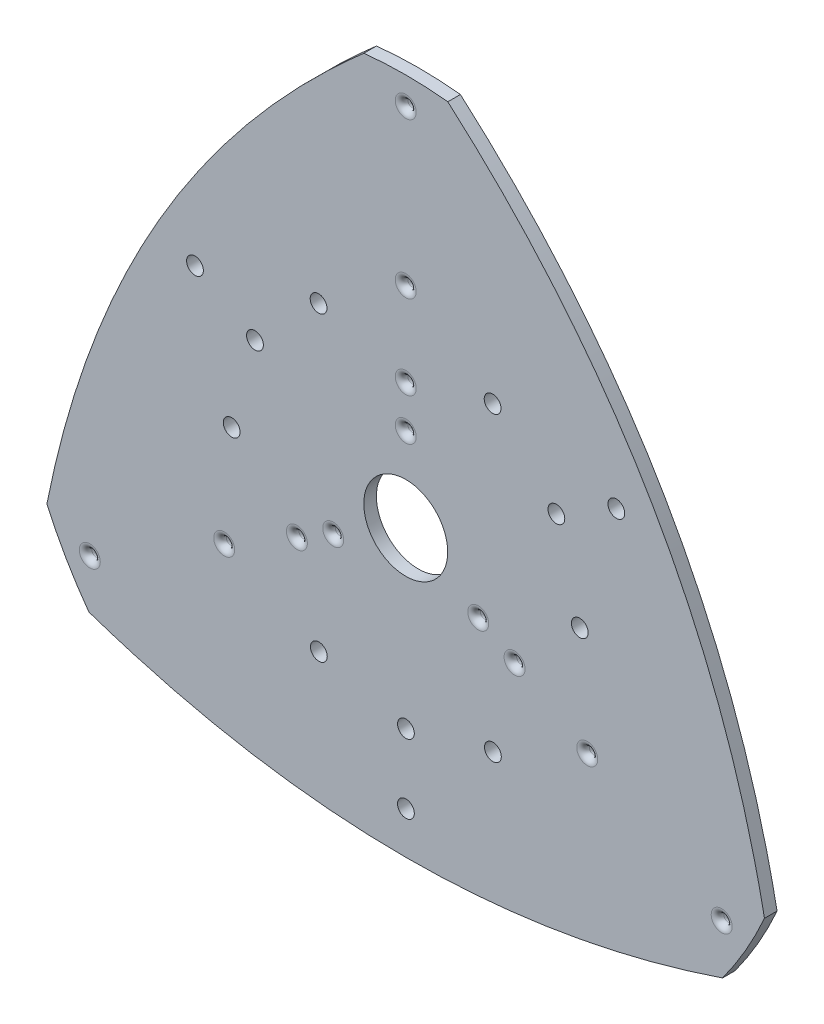
SolidWorks part; units mm, degrees
note: '?' marks a value the reader was unsure of.
ref_plane "前视基准面" through (0, 0, 0) normal (0, 0, 1) x (1, 0, 0)
ref_plane "上视基准面" through (0, 0, 0) normal (0, 1, 0) x (1, 0, 0)
ref_plane "右视基准面" through (0, 0, 0) normal (1, 0, 0) x (0, 0, -1)
other "Configuration Table"
sketch "草图1" plane through (0, 0, 0) normal (0, 0, 1) x (1, 0, 0)
  line L0 (0, -0.0456) -> (0, 19.9544) construction
  line L5 (0, -0.0456) -> (-35.9401, 20.7044) construction
  line L6 (0, -0.0456) -> (-23.3432, -0.0456)
  line L7 (0, 19.9544) -> (0, 29.9544) construction
  line L8 (0, 29.9544) -> (0, 49.9544) construction
  line L9 (0, -0.0456) -> (0, 86.9544) construction
  line L11 (0, -0.0456) -> (-58.8897, 33.9544)
  line L12 (-43.2617, -24.9772) -> (-75.3047, -43.4772) construction
  line L13 (-75.3047, -43.4772) -> (-80.9946, -46.7588) construction
  circle A0 centre (0, -0.0456) radius 10
  circle A1 centre (0, 86.9544) radius 1
  circle A2 centre (0, 49.9544) radius 1
  circle A3 centre (0, 29.9544) radius 1
  circle A4 centre (0, 19.9544) radius 1
  circle A6 centre (75.3047, -43.4772) radius 1
  circle A7 centre (43.2617, -24.9772) radius 1
  circle A8 centre (25.9412, -14.9772) radius 1
  circle A9 centre (17.281, -9.9772) radius 1
  circle A10 centre (-75.3047, -43.4772) radius 1
  circle A11 centre (-43.2617, -24.9772) radius 1
  circle A12 centre (-25.9412, -14.9772) radius 1
  circle A13 centre (-17.281, -9.9772) radius 1
  circle A17 centre (0, -0.0456) radius 93.5
  circle A18 centre (0, -0.0456) radius 41.5 construction
  circle A22 centre (0, -0.0456) radius 58 construction
  circle A53 centre (-35.9401, 20.7044) radius 2
  circle A54 centre (-20.7728, 35.9005) radius 2
  circle A56 centre (20.7044, 35.9401) radius 2
  circle A57 centre (35.9005, 20.7728) radius 2
  circle A58 centre (41.4772, 0.0395) radius 2
  circle A60 centre (20.7728, -35.9005) radius 2
  circle A61 centre (0.0395, -41.4772) radius 2
  circle A62 centre (-20.7044, -35.9401) radius 2
  circle A64 centre (-41.4772, -0.0395) radius 2
  circle A65 centre (-35.9005, -20.7728) radius 2 [skipped]
  circle A66 centre (35.9401, -20.7044) radius 2 [skipped]
  circle A67 centre (-0.0395, 41.4772) radius 2 [skipped]
  circle A68 centre (-50.2295, 28.9544) radius 2
  circle A69 centre (50.1899, 29.0228) radius 2
  circle A70 centre (0.0395, -57.9772) radius 2
  spline S0 degree 2 poles (-85.5203, -37.8415) (-70.0114, 40.3957) (-9.9857, 92.9196) knots 0 0 0 1 1 1
  spline S1 degree 2 poles (10.028, 92.9151) (70.0289, 40.3654) (85.5031, -37.8804) knots 0 0 0 1 1 1
  spline S2 degree 2 poles (75.4923, -55.2104) (-0.0175, -80.898) (-75.5174, -55.1761) knots 0 0 0 1 1 1
  point P0 (0, 0)
  point P31 (0, 0)
  point P39 (0, 0)
  point P46 (0, 0)
  point P49 (0, 0)
  point P66 (0, 0)
  point P79 (0, 0)
  point P96 (0, 0)
  dimension "D2" = 20
  dimension "D7" = 2
  dimension "D8" = 2
  dimension "D9" = 2
  dimension "D10" = 2
  dimension "D11" = 187
  dimension "D14" = 30
  dimension "D15" = 83
  dimension "D16" = 4
  dimension "D13" = 116
  dimension "D18" = 68
  dimension "D19" = 4
  dimension "D3" = 20
  dimension "D4" = 10
  dimension "D5" = 20
  dimension "D6" = 37
  dimension "D20" = 60
  dimension "D12" = 3
  dimension "D17" = 12
extrude "凸台-拉伸1" add sketch "草图1" along normal blind 3
ref_axis "基准轴1" through (0, -0.0456, 52.2092) along (0, 0, -1)?
fillet "圆角1" radius 1.5 24 edges at (76.3047, -43.4772, 0) (44.2617, -24.9772, 0) (26.9412, -14.9772, 0) (18.281, -9.9772, 0) (1, 86.9544, 0) (1, 49.9544, 0) (1, 29.9544, 0) (1, 19.9544, 0) (-16.281, -9.9772, 0) (-24.9412, -14.9772, 0) (-42.2617, -24.9772, 0) (-74.3047, -43.4772, 0) (76.3047, -43.4772, 3) (44.2617, -24.9772, 3) (26.9412, -14.9772, 3) (18.281, -9.9772, 3) (-74.3047, -43.4772, 3) (-42.2617, -24.9772, 3) (-24.9412, -14.9772, 3) (-16.281, -9.9772, 3) (1, 19.9544, 3) (1, 29.9544, 3) (1, 49.9544, 3) (1, 86.9544, 3)
